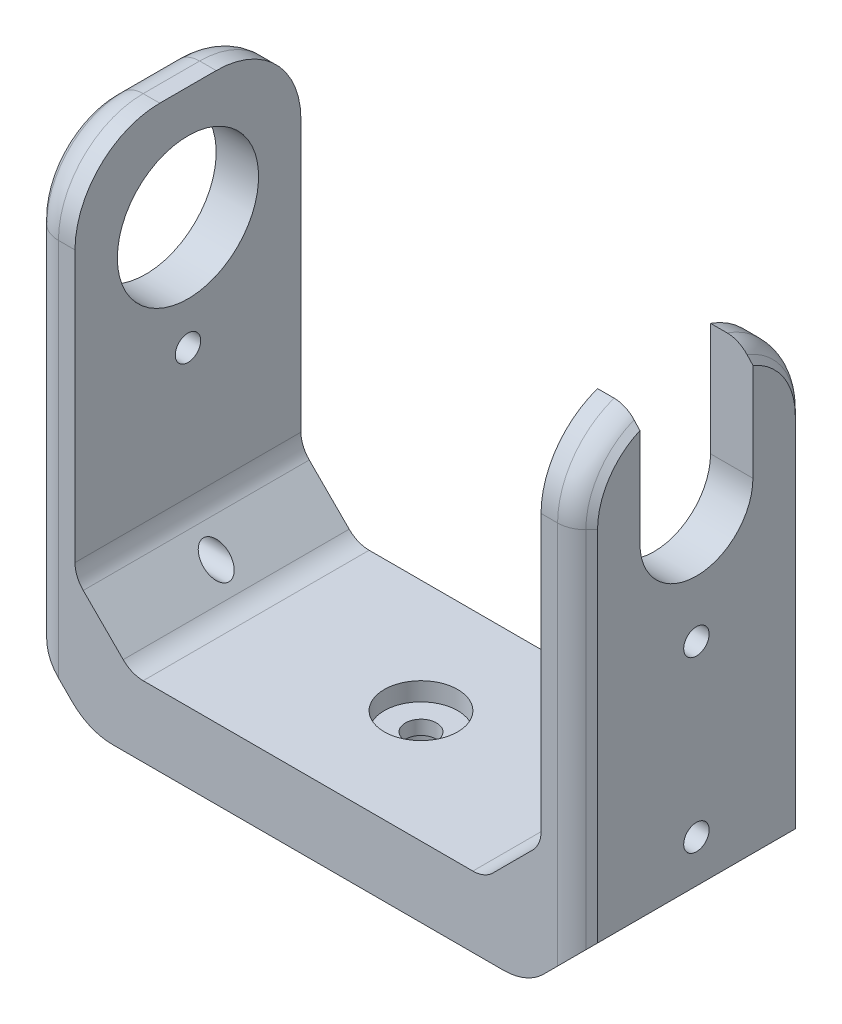
SolidWorks part; units mm, degrees
ref_plane "Front Plane" through (0, 0, 0) normal (0, 0, 1) x (1, 0, 0)
ref_plane "Top Plane" through (0, 0, 0) normal (0, 1, 0) x (1, 0, 0)
ref_plane "Right Plane" through (0, 0, 0) normal (1, 0, 0) x (0, 0, -1)
sketch "Sketch1" plane through (0, 0, 0) normal (0, 1, 0) x (1, 0, 0)
  line L0 (16.5, 8) -> (33, 16) construction
  line L1 (0, 0) -> (33, 0)
  line L2 (0, 0) -> (0, 16)
  line L3 (0, 16) -> (33, 16)
  line L4 (33, 0) -> (33, 16)
  line L5 (16.5, 8) -> (33, 0) construction
  line L6 (16.5, 8) -> (0, 16) construction
  circle A0 centre (16.5, 8) radius 2.4
  dimension "D1" = 4.8
  dimension "D2" = 16
  dimension "D3" = 33
extrude "Boss-Extrude1" add sketch "Sketch1" along normal blind 2.7
sketch "Sketch2" plane through (0, 2.7, 0) normal (0, 1, 0) x (1, 0, 0)
  line L1 (0, 16) -> (33, 16)
  line L2 (0, 16) -> (0, 0)
  line L3 (0, 0) -> (33, 0)
  line L4 (33, 16) -> (33, 0)
  circle A0 centre (16.5, 8) radius 1.1
  circle A2 centre (16.5, 8) radius 2.4 construction
  point P8 (0, 0)
  dimension "D1" = 2.2
extrude "Boss-Extrude2" add sketch "Sketch2" along normal blind 2.3
sketch "Sketch4" plane through (0, 0, 0) normal (-1, 0, 0) x (0, 0, 1)
  line L0 (-8, 27) -> (-16, 35) construction
  line L1 (-16, 0) -> (0, 0)
  line L2 (-16, 0) -> (-16, 35)
  line L3 (-16, 35) -> (0, 35)
  line L4 (0, 0) -> (0, 35)
  line L5 (-8, 27) -> (0, 35) construction
  line L6 (-16, 5) -> (0, 5) construction
  circle A0 centre (-8, 27) radius 5
  point P5 (-6.05, 19.9008)
  dimension "D1" = 10
  dimension "D2" = 22
  dimension "D3" = 8
extrude "Boss-Extrude3" add sketch "Sketch4" along normal blind 3
sketch "Sketch5" plane through (33, 0, 0) normal (1, 0, 0) x (0, 0, -1)
  line L0 (0, 5) -> (0, 35) construction
  line L1 (0, 35) -> (4, 35)
  line L2 (0, 35) -> (0, 0)
  line L3 (0, 0) -> (16, 0)
  line L4 (16, 35) -> (16, 0)
  line L5 (4, 27) -> (4, 35)
  line L6 (12, 27) -> (12, 35)
  line L7 (12, 35) -> (16, 35)
  arc A0 (4, 27) -> (12, 27) centre (8, 27) ccw
  dimension "D1" = 4
extrude "Boss-Extrude4" add sketch "Sketch5" along normal blind 3
fillet "Fillet1" radius 6 4 edges at (34.5, 35, -16) (-1.5, 35, -16) (34.5, 35, 0) (-1.5, 35, 0)
chamfer "Chamfer1" distance 4 angle 45 2 edges at (33, 5, -8) (0, 5, -8)
sketch "Sketch6" plane through (-3, 0, 0) normal (-1, 0, 0) x (0, 0, 1)
  line L0 (-8, 19) -> (-8, 27) construction
  circle A0 centre (-8, 19) radius 0.9
  circle A1 centre (-8, 7) radius 0.9
  point P4 (-4.8888, 10.3297)
  dimension "D1" = 1.8
  dimension "D2" = 8
  dimension "D3" = 12
extrude "Cut-Extrude1" cut sketch "Sketch6" against normal through all
chamfer "Chamfer2" distance 1 angle 45 9 edges at (36, 14.6716, -16) (36, 32.8072, -14.899) (36, 14.6716, 0) (36, 32.8072, -1.101) (-3, 14.5, 0) (-3, 14.5, -16) (-3, 33.2426, -1.7574) (-3, 33.2426, -14.2426) (-3, 35, -8)
fillet "Fillet3" radius 2 9 edges at (35, 14.6716, -16) (35, 14.6716, 0) (-2, 14.5, -16) (-2, 33.2426, -14.2426) (-2, 14.5, 0) (-2, 33.2426, -1.7574) (35, 32.8072, -14.899) (35, 32.8072, -1.101) (-2, 35, -8)
sketch "Sketch7" plane through (0, 5, 0) normal (0, 1, 0) x (1, 0, 0)
  circle A0 centre (16.5, 8) radius 2.6
  dimension "D1" = 5.2
extrude "Cut-Extrude2" cut sketch "Sketch7" against normal blind 1.3
fillet "Fillet4" radius 2 4 edges at (33, 9, -8) (29, 5, -8) (4, 5, -8) (0, 9, -8)
chamfer "Chamfer3" distance 4 angle 45 2 edges at (36, 0, -8) (-3, 0, -8)
fillet "Fillet7" radius 4 2 edges at (32, 0, -8) (1, 0, -8)
